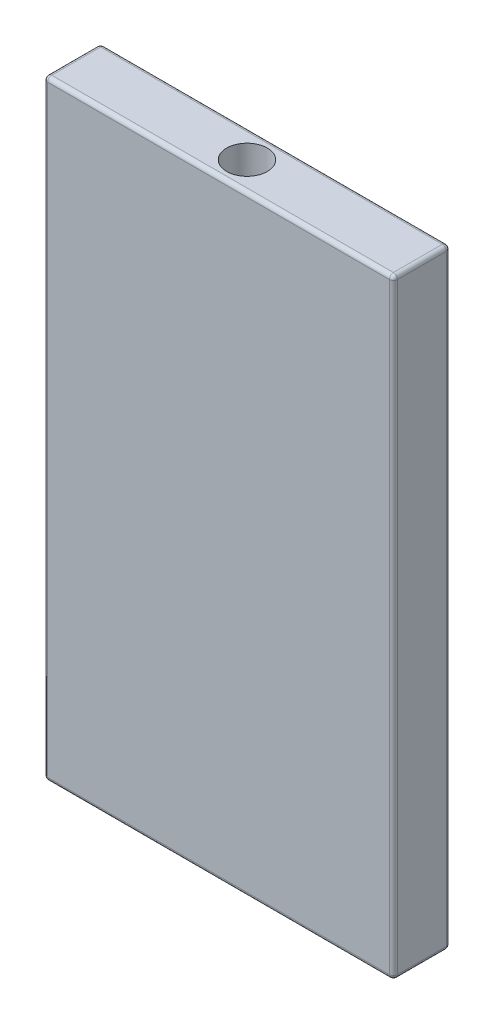
SolidWorks part; units mm, degrees
ref_plane "Front Plane" through (0, 0, 0) normal (0, 0, 1) x (1, 0, 0)
ref_plane "Top Plane" through (0, 0, 0) normal (0, 1, 0) x (1, 0, 0)
ref_plane "Right Plane" through (0, 0, 0) normal (1, 0, 0) x (0, 0, -1)
sketch "Sketch1" plane through (0, 0, 0) normal (0, 0, 1) x (1, 0, 0)
  line L1 (-21.5, 37.5) -> (21.5, 37.5)
  line L2 (-21.5, 37.5) -> (-21.5, -37.5)
  line L3 (-21.5, -37.5) -> (21.5, -37.5)
  line L4 (21.5, 37.5) -> (21.5, -37.5)
  line L5 (-21.5, 37.5) -> (21.5, -37.5) construction
  line L6 (-21.5, -37.5) -> (21.5, 37.5) construction
  point P0 (0, 0)
  dimension "D1" = 43
  dimension "D2" = 75
extrude "Boss-Extrude1" add sketch "Sketch1" along normal blind 7
sketch "Sketch2" plane through (0, 37.5, 0) normal (0, 1, 0) x (1, 0, 0)
  line L0 (0, 0) -> (0, -3.5) construction
  circle A0 centre (0, -3.5) radius 2.5
  dimension "D1" = 3.5
extrude "Cut-Extrude1" cut sketch "Sketch2" against normal up to next
fillet "Fillet1" radius 0.5 8 edges at (21.5, 0, 7) (0, -37.5, 7) (-21.5, 0, 7) (0, 37.5, 7) (0, 37.5, 0) (21.5, 0, 0) (0, -37.5, 0) (-21.5, 0, 0)
fillet "Fillet2" radius 0.5 12 edges at (21.3536, -37.3536, 6.8536) (21.3536, -37.3536, 0.1464) (-21.3536, -37.3536, 6.8536) (-21.3536, -37.3536, 0.1464) (-21.3536, 37.3536, 6.8536) (-21.3536, 37.3536, 0.1464) (21.3536, 37.3536, 6.8536) (21.3536, 37.3536, 0.1464) (21.5, -37.5, 3.5) (-21.5, -37.5, 3.5) (-21.5, 37.5, 3.5) (21.5, 37.5, 3.5)
